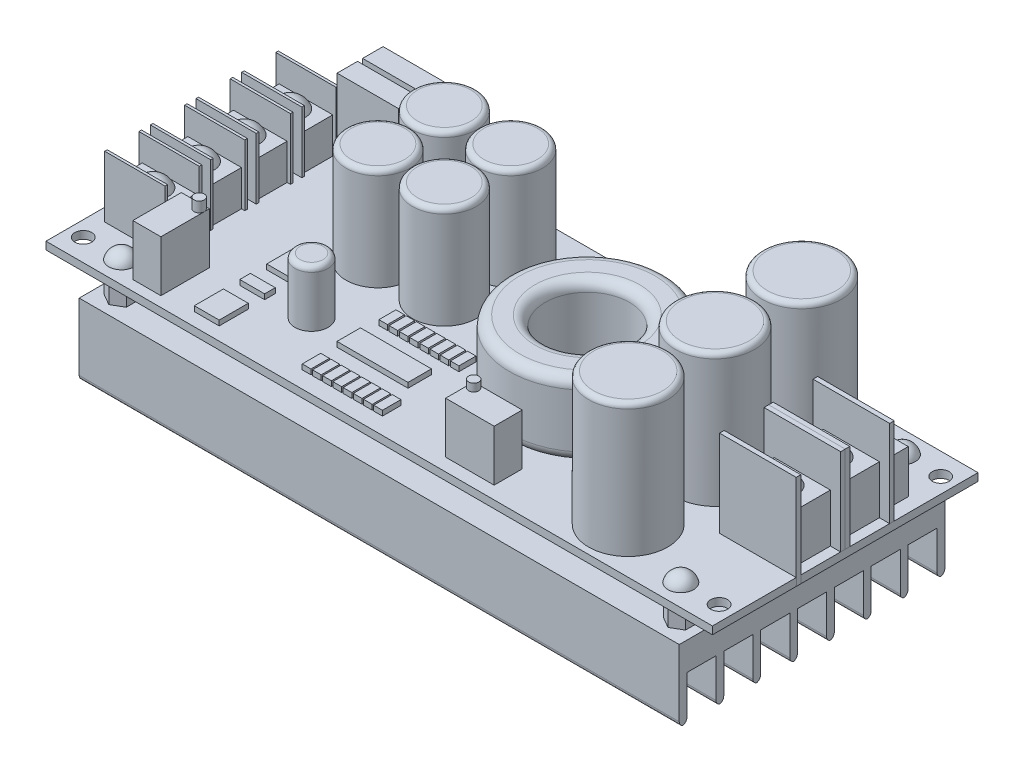
SolidWorks part; units mm, degrees
ref_plane "Alzado" through (0, 0, 0) normal (0, 0, 1) x (1, 0, 0)
ref_plane "Planta" through (0, 0, 0) normal (0, 1, 0) x (1, 0, 0)
ref_plane "Vista lateral" through (0, 0, 0) normal (1, 0, 0) x (0, 0, -1)
sketch "Croquis1" plane through (0, 0, 0) normal (0, 1, 0) x (1, 0, 0)
  line L0 (0, -26) -> (0, 26) construction
  line L1 (-65.25, 26) -> (65.25, 26)
  line L2 (-65.25, 26) -> (-65.25, -26)
  line L3 (-65.25, -26) -> (65.25, -26)
  line L4 (65.25, 26) -> (65.25, -26)
  line L5 (-65.25, 26) -> (65.25, -26) construction
  line L6 (-65.25, -26) -> (65.25, 26) construction
  line L7 (-65.25, 0) -> (65.25, 0) construction
  circle A0 centre (62.25, 21.7) radius 1.65
  circle A1 centre (62.25, -21.7) radius 1.65
  circle A2 centre (-62.25, -21.7) radius 1.65
  circle A3 centre (-62.25, 21.7) radius 1.65
  circle A4 centre (54.75, 21.7) radius 1.65
  circle A5 centre (54.75, -21.7) radius 1.65
  circle A6 centre (-54.75, -21.7) radius 1.65
  circle A7 centre (-54.75, 21.7) radius 1.65
  point P0 (0, 0)
  point P9 (0, 0)
  point P12 (0, 0)
  dimension "D3" = 3.3
  dimension "D1" = 52
  dimension "D2" = 130.5
  dimension "D4" = 3
  dimension "D5" = 4.3
  dimension "D6" = 7.5
extrude "Saliente-Extruir1" add sketch "Croquis1" along normal blind 1.5
sketch "Croquis2" plane through (0, 1.5, 0) normal (0, 1, 0) x (1, 0, 0)
  line L1 (54.75, 19.2) -> (56.9151, 20.45)
  line L2 (56.9151, 20.45) -> (56.9151, 22.95)
  line L3 (56.9151, 22.95) -> (54.75, 24.2)
  line L4 (54.75, 24.2) -> (52.5849, 22.95)
  line L5 (52.5849, 22.95) -> (52.5849, 20.45)
  line L6 (52.5849, 20.45) -> (54.75, 19.2)
  circle A0 centre (54.75, 21.7) radius 2.1651 construction
  dimension "D1" = 2.5
extrude "Saliente-Extruir2" add sketch "Croquis2" against normal blind 4.9 and the other way up to surface from surface separate body other way up to face at (-54.75, 1.5, 23.35) starting at face at (0, 0, 0)
ref_plane "Plano1" through (54.75, 0, 0) normal (1, 0, 0) x (0, 0, -1)
sketch "Croquis3" plane through (54.75, 0, 0) normal (1, 0, 0) x (0, 0, -1)
  line L0 (24.2, 1.5) -> (19.2, 1.5) construction
  line L1 (21.7, 1.5) -> (21.7, 3.5) construction
  line L2 (21.7, 1.5) -> (24.2, 1.5)
  line L3 (21.7, 1.5) -> (21.7, 3.5)
  arc A0 (21.7, 3.5) -> (24.2, 1.5) centre (21.7, 0.9375) cw
  dimension "D1" = 2
revolve "Revolución1" add sketch "Croquis3" angle 360 about L3
combine bodies "Combinar1" operation type add bodies to combine 102 103
mirror "Simetría3" about plane through (0, 0, 0) normal (0, 0, 1) of bodies 104
mirror "Simetría4" about plane through (0, 0, 0) normal (1, 0, 0) of bodies 104 108
sketch "Croquis4" plane through (0, -4.9, 0) normal (0, -1, 0) x (1, 0, 0)
  line L1 (-58.75, 26) -> (58.75, 26)
  line L2 (-58.75, 26) -> (-58.75, -26)
  line L3 (-58.75, -26) -> (58.75, -26)
  line L4 (58.75, 26) -> (58.75, -26)
  line L5 (-58.75, 26) -> (58.75, -26) construction
  line L6 (-58.75, -26) -> (58.75, 26) construction
  point P0 (0, 0)
  dimension "D1" = 52
  dimension "D2" = 117.5
extrude "Saliente-Extruir3" add sketch "Croquis4" along normal blind 5.5
sketch "Croquis5" plane through (0, -10.4, 0) normal (0, -1, 0) x (1, 0, 0)
  line L0 (58.75, -26) -> (58.75, 26) construction
  line L1 (-58.75, 26) -> (58.75, 26)
  line L2 (-58.75, 26) -> (-58.75, 24.5)
  line L3 (-58.75, 24.5) -> (58.75, 24.5)
  line L4 (58.75, 26) -> (58.75, 24.5)
  line L5 (-58.75, 18.7857) -> (-58.75, 17.2857)
  line L6 (-58.75, 18.7857) -> (58.75, 18.7857)
  line L7 (58.75, 18.7857) -> (58.75, 17.2857)
  line L8 (-58.75, 17.2857) -> (58.75, 17.2857)
  line L9 (-58.75, 11.5714) -> (-58.75, 10.0714)
  line L10 (-58.75, 11.5714) -> (58.75, 11.5714)
  line L11 (58.75, 11.5714) -> (58.75, 10.0714)
  line L12 (-58.75, 10.0714) -> (58.75, 10.0714)
  line L13 (-58.75, 4.3571) -> (-58.75, 2.8571)
  line L14 (-58.75, 4.3571) -> (58.75, 4.3571)
  line L15 (58.75, 4.3571) -> (58.75, 2.8571)
  line L16 (-58.75, 2.8571) -> (58.75, 2.8571)
  line L17 (-58.75, -2.8571) -> (-58.75, -4.3571)
  line L18 (-58.75, -2.8571) -> (58.75, -2.8571)
  line L19 (58.75, -2.8571) -> (58.75, -4.3571)
  line L20 (-58.75, -4.3571) -> (58.75, -4.3571)
  line L21 (-58.75, -10.0714) -> (-58.75, -11.5714)
  line L22 (-58.75, -10.0714) -> (58.75, -10.0714)
  line L23 (58.75, -10.0714) -> (58.75, -11.5714)
  line L24 (-58.75, -11.5714) -> (58.75, -11.5714)
  line L25 (-58.75, -17.2857) -> (-58.75, -18.7857)
  line L26 (-58.75, -17.2857) -> (58.75, -17.2857)
  line L27 (58.75, -17.2857) -> (58.75, -18.7857)
  line L28 (-58.75, -18.7857) -> (58.75, -18.7857)
  line L29 (-58.75, -24.5) -> (-58.75, -26)
  line L30 (-58.75, -24.5) -> (58.75, -24.5)
  line L31 (58.75, -24.5) -> (58.75, -26)
  line L32 (-58.75, -26) -> (58.75, -26)
  line L33 (-58.75, 26) -> (-58.75, -26) construction
  line L34 (-58.75, -26) -> (58.75, -26) construction
  dimension "D1" = 1.5
  dimension "D2" = 8
extrude "Saliente-Extruir4" add sketch "Croquis5" along normal blind 8.6
fillet "Redondeo1" radius 1 16 edges at (0, -19, -26) (0, -19, -24.5) (0, -19, -18.7857) (0, -19, -17.2857) (0, -19, -11.5714) (0, -19, -10.0714) (0, -19, -4.3571) (0, -19, -2.8571) (0, -19, 2.8571) (0, -19, 4.3571) (0, -19, 10.0714) (0, -19, 11.5714) (0, -19, 17.2857) (0, -19, 18.7857) (0, -19, 24.5) (0, -19, 26)
sketch "Croquis7" plane through (0, 0, 0) normal (0, 1, 0) x (1, 0, 0)
  line L0 (-65.25, 0) -> (65.25, 0) construction
  line L1 (-65.25, 26) -> (-65.25, -26) construction
  line L2 (65.25, -26) -> (65.25, 26) construction
  line L4 (65.25, 0) -> (50.25, 0)
  line L5 (65.25, 0) -> (65.25, -0.9)
  line L6 (65.25, -0.9) -> (50.25, -0.9)
  line L7 (50.25, 0) -> (50.25, -0.9)
  line L8 (52.25, -0.9) -> (63.25, -0.9)
  line L9 (52.25, -0.9) -> (52.25, -8.7)
  line L10 (52.25, -8.7) -> (63.25, -8.7)
  line L11 (63.25, -0.9) -> (63.25, -8.7)
  line L12 (50.25, -8.7) -> (65.25, -8.7)
  line L13 (50.25, -8.7) -> (50.25, -9.6)
  line L14 (50.25, -9.6) -> (65.25, -9.6)
  line L15 (65.25, -8.7) -> (65.25, -9.6)
  point P13 (57.75, 0)
  point P14 (57.75, -8.7)
  dimension "D1" = 0.9
  dimension "D2" = 15
  dimension "D3" = 11
  dimension "D4" = 7.8
extrude "Saliente-Extruir5" add sketch "Croquis7" along normal blind 18.5 separate body contours L15 L14 L13 L12 | L5 L6 L7 L4
sketch "Croquis8" plane through (0, 0, 0) normal (0, 1, 0) x (1, 0, 0)
  line L0 (65.25, -0.9) -> (50.25, -0.9) construction
  line L1 (52.25, -8.7) -> (63.25, -8.7) construction
  line L2 (52.25, -0.9) -> (52.25, -8.7) construction
  line L3 (63.25, -0.9) -> (63.25, -8.7) construction
  line L4 (63.25, -0.9) -> (52.25, -0.9)
  line L5 (52.25, -8.7) -> (63.25, -8.7)
  line L6 (52.25, -0.9) -> (52.25, -8.7)
  line L7 (63.25, -0.9) -> (63.25, -8.7)
extrude "Saliente-Extruir6" add sketch "Croquis8" along normal blind 11 separate body
combine bodies "Combinar2" operation type add bodies to combine 115 113 114
ref_plane "Plano2" through (57.75, 0, 0) normal (1, 0, 0) x (0, 0, -1)
sketch "Croquis9" plane through (57.75, 0, 0) normal (1, 0, 0) x (0, 0, -1)
  line L0 (-4.8, 11) -> (-4.8, 13)
  line L1 (-8.7, 11) -> (-0.9, 11) construction
  line L2 (-4.8, 11) -> (-1.8, 11)
  arc A0 (-4.8, 13) -> (-1.8, 11) centre (-4.8, 9.75) cw
  dimension "D1" = 2
  dimension "D2" = 3
revolve "Revolución2" add sketch "Croquis9" angle 360 about L0
mirror "Simetría5" about plane through (0, 0, 0) normal (0, 0, 1) of bodies 116 117
sketch "Croquis10" plane through (0, 0, 0) normal (0, 1, 0) x (1, 0, 0)
  line L0 (52.25, 8.7) -> (63.25, 8.7) construction
  line L1 (53, 15.1) -> (62.5, 15.1)
  line L2 (53, 15.1) -> (53, 10.1)
  line L3 (53, 10.1) -> (62.5, 10.1)
  line L4 (62.5, 15.1) -> (62.5, 10.1)
  line L5 (50.25, 9.6) -> (65.25, 9.6) construction
  point P6 (57.75, 8.7)
  point P7 (57.75, 10.1)
  dimension "D1" = 0.5
  dimension "D2" = 5
  dimension "D3" = 9.5
extrude "Saliente-Extruir7" add sketch "Croquis10" along normal blind 10 separate body
sketch "Croquis11" plane through (0, 10, 0) normal (0, 1, 0) x (1, 0, 0)
  line L0 (62.5, 10.1) -> (62.5, 15.1) construction
  line L1 (53, 10.1) -> (62.5, 10.1) construction
  circle A0 centre (61.5, 11.1) radius 1
  dimension "D1" = 2
extrude "Saliente-Extruir8" add sketch "Croquis11" along normal blind 1.5 separate body
sketch "Croquis12" plane through (0, 1.5, 0) normal (0, 1, 0) x (1, 0, 0)
  line L0 (65.25, -26) -> (65.25, 26) construction
  line L1 (65.25, 26) -> (-65.25, 26) construction
  line L2 (-65.25, -26) -> (65.25, -26) construction
  circle A0 centre (39.75, 17) radius 7.75
  circle A1 centre (39.75, 0) radius 7.75
  circle A2 centre (39.75, -17) radius 7.75
  dimension "D2" = 9
  dimension "15." = 15.5
  dimension "D1" = 25.5
  dimension "D4" = 9
  dimension "D3" = 3
extrude "Saliente-Extruir9" add sketch "Croquis12" along normal blind 26 separate body
sketch "Croquis14" plane through (0, 0, 0) normal (0, 0, 1) x (1, 0, 0)
  line L0 (-65.25, 1.5) -> (65.25, 1.5) construction
  line L1 (28, 1.5) -> (25, 1.5)
  line L2 (30, 3.5) -> (30, 14)
  line L3 (28, 16) -> (25, 16)
  line L4 (23, 3.5) -> (23, 14)
  line L5 (32, 27.5) -> (32, 1.5) construction
  line L6 (14.75, 1.5) -> (14.75, 16) construction
  arc A0 (28, 1.5) -> (30, 3.5) centre (28, 3.5) ccw
  arc A1 (25, 1.5) -> (23, 3.5) centre (25, 3.5) cw
  arc A2 (30, 14) -> (28, 16) centre (28, 14) ccw
  arc A3 (25, 16) -> (23, 14) centre (25, 14) ccw
  point P10 (23, 8.75)
  point P14 (30, 1.5)
  point P21 (23, 16)
  dimension "D5" = 2
  dimension "D1" = 2
  dimension "D2" = 14.5
  dimension "D3" = 7
  dimension "D4" = 8.25
revolve "Revolución3" add sketch "Croquis14" angle 360 about L6
sketch "Croquis15" plane through (0, 1.5, 0) normal (0, 1, 0) x (1, 0, 0)
  line L0 (65.25, -26) -> (65.25, 26) construction
  line L1 (10.5, -18) -> (20, -18)
  line L2 (10.5, -18) -> (10.5, -23.5)
  line L3 (10.5, -23.5) -> (20, -23.5)
  line L4 (20, -18) -> (20, -23.5)
  line L5 (-65.25, -26) -> (65.25, -26) construction
  point P4 (15.25, -18)
  dimension "D1" = 50
  dimension "D2" = 9.5
  dimension "D3" = 5.5
  dimension "D4" = 2.5
extrude "Saliente-Extruir10" add sketch "Croquis15" along normal blind 10 separate body
sketch "Croquis16" plane through (0, 11.5, 0) normal (0, 1, 0) x (1, 0, 0)
  line L0 (20, -18) -> (10.5, -18) construction
  line L1 (10.5, -18) -> (10.5, -23.5) construction
  circle A0 centre (11.5, -19) radius 1
  circle A1 centre (61.5, 11.1) radius 1 construction
extrude "Saliente-Extruir11" add sketch "Croquis16" along normal blind 1.5 separate body
fillet "Redondeo2" radius 1 1 edges at (39.75, 27.5, 24.75)
fillet "Redondeo3" radius 1 1 edges at (39.75, 27.5, 7.75)
fillet "Redondeo4" radius 1 1 edges at (39.75, 27.5, -9.25)
sketch "Croquis17" plane through (0, 1.5, 0) normal (0, 1, 0) x (1, 0, 0)
  line L0 (-65.25, 26) -> (-65.25, -26) construction
  line L1 (-62.75, 17) -> (-50.95, 17)
  line L2 (-62.75, 17) -> (-62.75, 16.5)
  line L3 (-62.75, 16.5) -> (-50.95, 16.5)
  line L4 (-50.95, 17) -> (-50.95, 16.5)
  line L5 (65.25, 26) -> (-65.25, 26) construction
  line L6 (-62.75, 10.3) -> (-62.75, 9.8)
  line L7 (-62.75, 10.3) -> (-50.95, 10.3)
  line L8 (-50.95, 10.3) -> (-50.95, 9.8)
  line L9 (-62.75, 9.8) -> (-50.95, 9.8)
  line L10 (-62.75, 1.3667) -> (-62.75, 0.8667)
  line L11 (-62.75, 0.8667) -> (-50.95, 0.8667)
  line L12 (-50.95, 1.3667) -> (-50.95, 0.8667)
  line L13 (-62.75, 1.3667) -> (-50.95, 1.3667)
  line L14 (-62.75, 8.0667) -> (-62.75, 7.5667)
  line L15 (-62.75, 8.0667) -> (-50.95, 8.0667)
  line L16 (-50.95, 8.0667) -> (-50.95, 7.5667)
  line L17 (-62.75, 7.5667) -> (-50.95, 7.5667)
  line L18 (-62.75, -7.5667) -> (-62.75, -8.0667)
  line L19 (-62.75, -8.0667) -> (-50.95, -8.0667)
  line L20 (-50.95, -7.5667) -> (-50.95, -8.0667)
  line L21 (-62.75, -7.5667) -> (-50.95, -7.5667)
  line L22 (-62.75, -0.8667) -> (-62.75, -1.3667)
  line L23 (-62.75, -0.8667) -> (-50.95, -0.8667)
  line L24 (-50.95, -0.8667) -> (-50.95, -1.3667)
  line L25 (-62.75, -1.3667) -> (-50.95, -1.3667)
  line L26 (-62.75, -16.5) -> (-62.75, -17)
  line L27 (-62.75, -17) -> (-50.95, -17)
  line L28 (-50.95, -16.5) -> (-50.95, -17)
  line L29 (-62.75, -16.5) -> (-50.95, -16.5)
  line L30 (-62.75, -9.8) -> (-62.75, -10.3)
  line L31 (-62.75, -9.8) -> (-50.95, -9.8)
  line L32 (-50.95, -9.8) -> (-50.95, -10.3)
  line L33 (-62.75, -10.3) -> (-50.95, -10.3)
  line L34 (-65.25, -26) -> (65.25, -26) construction
  dimension "D1" = 0.5
  dimension "D2" = 11.8
  dimension "D3" = 2.5
  dimension "D4" = 9
  dimension "D6" = 6.2
  dimension "D8" = 9
  dimension "D5" = 2
  dimension "D7" = 4
extrude "Saliente-Extruir12" add sketch "Croquis17" along normal blind 12 separate body
sketch "Croquis18" plane through (0, 1.5, 0) normal (0, 1, 0) x (1, 0, 0)
  line L0 (-62.75, 16.5) -> (-50.95, 16.5) construction
  line L1 (-62.1, 16.5) -> (-51.6, 16.5)
  line L2 (-62.1, 16.5) -> (-62.1, 10.3)
  line L3 (-62.1, 10.3) -> (-51.6, 10.3)
  line L4 (-51.6, 16.5) -> (-51.6, 10.3)
  line L5 (-50.95, 10.3) -> (-62.75, 10.3) construction
  line L6 (-62.75, 9.8) -> (-50.95, 9.8) construction
  line L7 (-62.1, 7.5667) -> (-62.1, 1.3667)
  line L8 (-62.1, 7.5667) -> (-51.6, 7.5667)
  line L9 (-51.6, 7.5667) -> (-51.6, 1.3667)
  line L10 (-62.1, 1.3667) -> (-51.6, 1.3667)
  line L11 (-62.1, -1.3667) -> (-62.1, -7.5667)
  line L12 (-62.1, -1.3667) -> (-51.6, -1.3667)
  line L13 (-51.6, -1.3667) -> (-51.6, -7.5667)
  line L14 (-62.1, -7.5667) -> (-51.6, -7.5667)
  line L15 (-62.1, -10.3) -> (-62.1, -16.5)
  line L16 (-62.1, -10.3) -> (-51.6, -10.3)
  line L17 (-51.6, -10.3) -> (-51.6, -16.5)
  line L18 (-62.1, -16.5) -> (-51.6, -16.5)
  point P8 (-56.85, 9.8)
  point P11 (-56.85, 16.5)
  dimension "D1" = 10.5
  dimension "D2" = 4
extrude "Saliente-Extruir13" add sketch "Croquis18" along normal blind 7 separate body
combine bodies "Combinar3" operation type add bodies to combine 136 135 134
combine bodies "Combinar4" operation type add bodies to combine 139 133 132
combine bodies "Combinar5" operation type add bodies to combine 138 131 130
combine bodies "Combinar6" operation type add bodies to combine 137 129 128
ref_plane "Plano3" through (-56.85, 0, 0) normal (1, 0, 0) x (0, 0, -1)
sketch "Croquis19" plane through (-56.85, 0, 0) normal (1, 0, 0) x (0, 0, -1)
  line L0 (13.4, 8.5) -> (13.4, 10.5)
  line L1 (16.5, 8.5) -> (10.3, 8.5) construction
  line L2 (13.4, 8.5) -> (10.4, 8.5)
  arc A0 (13.4, 10.5) -> (10.4, 8.5) centre (13.4, 7.25) ccw
  dimension "D1" = 2
  dimension "D2" = 3
revolve "Revolución4" add sketch "Croquis19" angle 360 about L0
sketch "Croquis20" plane through (-56.85, 0, 0) normal (1, 0, 0) x (0, 0, -1)
  line L0 (4.4667, 8.5) -> (4.4667, 10.5)
  line L1 (7.5667, 8.5) -> (1.3667, 8.5) construction
  line L2 (4.4667, 8.5) -> (1.4667, 8.5)
  arc A0 (4.4667, 10.5) -> (1.4667, 8.5) centre (4.4667, 7.25) ccw
  dimension "D1" = 2
  dimension "D2" = 3
revolve "Revolución5" add sketch "Croquis20" angle 360 about L0
mirror "Simetría6" about plane through (0, 0, 0) normal (0, 0, 1) of bodies 144 145
sketch "Croquis21" plane through (0, 1.5, 0) normal (0, 1, 0) x (1, 0, 0)
  line L0 (20, -18) -> (10.5, -18) construction
  line L1 (-50.25, -24) -> (-44.75, -24)
  line L2 (-50.25, -24) -> (-50.25, -14.5)
  line L3 (-50.25, -14.5) -> (-44.75, -14.5)
  line L4 (-44.75, -24) -> (-44.75, -14.5)
  line L5 (10.5, -18) -> (10.5, -23.5) construction
  line L6 (-65.25, -26) -> (65.25, -26) construction
  line L7 (-65.25, 26) -> (-65.25, -26) construction
  dimension "D1" = 2
  dimension "D2" = 15
extrude "Saliente-Extruir14" add sketch "Croquis21" along normal blind 10 separate body
sketch "Croquis22" plane through (0, 11.5, 0) normal (0, 1, 0) x (1, 0, 0)
  line L0 (-44.75, -24) -> (-44.75, -14.5) construction
  line L1 (-44.75, -14.5) -> (-50.25, -14.5) construction
  circle A0 centre (-45.75, -15.5) radius 1
  circle A1 centre (11.5, -19) radius 1 construction
extrude "Saliente-Extruir15" add sketch "Croquis22" along normal blind 2 separate body
sketch "Croquis23" plane through (0, 1.5, 0) normal (0, 1, 0) x (1, 0, 0)
  line L0 (65.25, 26) -> (-65.25, 26) construction
  line L1 (-65.25, 26) -> (-65.25, -26) construction
  circle A0 centre (-29.25, 16) radius 6.25
  circle A1 centre (-16.25, 16) radius 6.25
  circle A2 centre (-16.25, 3) radius 6.25
  circle A3 centre (-29.25, 3) radius 6.25
  dimension "D1" = 12.5
  dimension "D2" = 10
  dimension "D3" = 36
  dimension "D6" = 13
  dimension "D7" = 13
  dimension "D4" = 2
  dimension "D5" = 2
extrude "Saliente-Extruir16" add sketch "Croquis23" along normal blind 20 separate body
fillet "Redondeo5" radius 1 1 edges at (-16.25, 21.5, -9.75)
fillet "Redondeo6" radius 1 1 edges at (-16.25, 21.5, 3.25)
fillet "Redondeo7" radius 1 1 edges at (-29.25, 21.5, 3.25)
fillet "Redondeo8" radius 1 1 edges at (-29.25, 21.5, -9.75)
sketch "Croquis24" plane through (0, 1.5, 0) normal (0, 1, 0) x (1, 0, 0)
  line L0 (-65.25, -26) -> (65.25, -26) construction
  line L1 (-65.25, 26) -> (-65.25, -26) construction
  circle A0 centre (-26.25, -13) radius 3.25
  dimension "D1" = 6.5
  dimension "D2" = 13
  dimension "D3" = 39
extrude "Saliente-Extruir17" add sketch "Croquis24" along normal blind 11 separate body
fillet "Redondeo9" radius 1 1 edges at (-26.25, 12.5, 16.25)
sketch "Croquis25" plane through (0, 1.5, 0) normal (0, 1, 0) x (1, 0, 0)
  line L1 (-18.766, -10.9121) -> (-4.8653, -10.9121)
  line L2 (-18.766, -10.9121) -> (-18.766, -15.4993)
  line L3 (-18.766, -15.4993) -> (-4.8653, -15.4993)
  line L4 (-4.8653, -10.9121) -> (-4.8653, -15.4993)
  line L5 (-38.7831, -17.7235) -> (-33.9178, -17.7235)
  line L6 (-38.7831, -17.7235) -> (-38.7831, -23.4228)
  line L7 (-38.7831, -23.4228) -> (-33.9178, -23.4228)
  line L8 (-33.9178, -17.7235) -> (-33.9178, -23.4228)
  line L9 (-38.7831, -12.4412) -> (-33.9178, -12.4412)
  line L10 (-38.7831, -12.4412) -> (-38.7831, -14.5263)
  line L11 (-38.7831, -14.5263) -> (-33.9178, -14.5263)
  line L12 (-33.9178, -12.4412) -> (-33.9178, -14.5263)
  line L13 (-38.7831, -9.244) -> (-33.9178, -9.244)
  line L14 (-38.7831, -9.244) -> (-38.7831, -4.3787)
  line L15 (-38.7831, -4.3787) -> (-33.9178, -4.3787)
  line L16 (-33.9178, -9.244) -> (-33.9178, -4.3787)
extrude "Saliente-Extruir18" add sketch "Croquis25" along normal blind 1 separate body
sketch "Croquis26" plane through (0, 1.5, 0) normal (0, 1, 0) x (1, 0, 0)
  line L0 (-16.349, -7.7149) -> (-16.349, -4.3787)
  line L1 (-18.349, -19.1135) -> (-16.6396, -19.1135)
  line L2 (-18.349, -19.1135) -> (-18.349, -22.7277)
  line L3 (-18.349, -22.7277) -> (-16.6396, -22.7277)
  line L4 (-16.6396, -19.1135) -> (-16.6396, -22.7277)
  line L5 (-18.349, -7.7149) -> (-16.6809, -7.7149)
  line L6 (-18.349, -7.7149) -> (-18.349, -4.3787)
  line L7 (-18.349, -4.3787) -> (-16.6809, -4.3787)
  line L8 (-16.6809, -7.7149) -> (-16.6809, -4.3787)
  line L9 (-16.349, -7.7149) -> (-14.6809, -7.7149)
  line L10 (-14.6809, -7.7149) -> (-14.6809, -4.3787)
  line L11 (-16.349, -4.3787) -> (-14.6809, -4.3787)
  line L12 (-16.349, -19.1135) -> (-16.349, -22.7277)
  line L13 (-16.349, -19.1135) -> (-14.6396, -19.1135)
  line L14 (-14.6396, -19.1135) -> (-14.6396, -22.7277)
  line L15 (-16.349, -22.7277) -> (-14.6396, -22.7277)
  line L16 (-14.349, -7.7149) -> (-14.349, -4.3787)
  line L17 (-14.349, -7.7149) -> (-12.6809, -7.7149)
  line L18 (-12.6809, -7.7149) -> (-12.6809, -4.3787)
  line L19 (-14.349, -4.3787) -> (-12.6809, -4.3787)
  line L20 (-14.349, -19.1135) -> (-14.349, -22.7277)
  line L21 (-14.349, -19.1135) -> (-12.6396, -19.1135)
  line L22 (-12.6396, -19.1135) -> (-12.6396, -22.7277)
  line L23 (-14.349, -22.7277) -> (-12.6396, -22.7277)
  line L24 (-12.349, -7.7149) -> (-12.349, -4.3787)
  line L25 (-12.349, -7.7149) -> (-10.6809, -7.7149)
  line L26 (-10.6809, -7.7149) -> (-10.6809, -4.3787)
  line L27 (-12.349, -4.3787) -> (-10.6809, -4.3787)
  line L28 (-12.349, -19.1135) -> (-12.349, -22.7277)
  line L29 (-12.349, -19.1135) -> (-10.6396, -19.1135)
  line L30 (-10.6396, -19.1135) -> (-10.6396, -22.7277)
  line L31 (-12.349, -22.7277) -> (-10.6396, -22.7277)
  line L32 (-10.349, -7.7149) -> (-10.349, -4.3787)
  line L33 (-10.349, -7.7149) -> (-8.6809, -7.7149)
  line L34 (-8.6809, -7.7149) -> (-8.6809, -4.3787)
  line L35 (-10.349, -4.3787) -> (-8.6809, -4.3787)
  line L36 (-10.349, -19.1135) -> (-10.349, -22.7277)
  line L37 (-10.349, -19.1135) -> (-8.6396, -19.1135)
  line L38 (-8.6396, -19.1135) -> (-8.6396, -22.7277)
  line L39 (-10.349, -22.7277) -> (-8.6396, -22.7277)
  line L40 (-8.349, -7.7149) -> (-8.349, -4.3787)
  line L41 (-8.349, -7.7149) -> (-6.6809, -7.7149)
  line L42 (-6.6809, -7.7149) -> (-6.6809, -4.3787)
  line L43 (-8.349, -4.3787) -> (-6.6809, -4.3787)
  line L44 (-8.349, -19.1135) -> (-8.349, -22.7277)
  line L45 (-8.349, -19.1135) -> (-6.6396, -19.1135)
  line L46 (-6.6396, -19.1135) -> (-6.6396, -22.7277)
  line L47 (-8.349, -22.7277) -> (-6.6396, -22.7277)
  line L48 (-6.349, -7.7149) -> (-6.349, -4.3787)
  line L49 (-6.349, -7.7149) -> (-4.6809, -7.7149)
  line L50 (-4.6809, -7.7149) -> (-4.6809, -4.3787)
  line L51 (-6.349, -4.3787) -> (-4.6809, -4.3787)
  line L52 (-6.349, -19.1135) -> (-6.349, -22.7277)
  line L53 (-6.349, -19.1135) -> (-4.6396, -19.1135)
  line L54 (-4.6396, -19.1135) -> (-4.6396, -22.7277)
  line L55 (-6.349, -22.7277) -> (-4.6396, -22.7277)
  line L56 (-4.349, -7.7149) -> (-4.349, -4.3787)
  line L57 (-4.349, -7.7149) -> (-2.6809, -7.7149)
  line L58 (-2.6809, -7.7149) -> (-2.6809, -4.3787)
  line L59 (-4.349, -4.3787) -> (-2.6809, -4.3787)
  line L60 (-4.349, -19.1135) -> (-4.349, -22.7277)
  line L61 (-4.349, -19.1135) -> (-2.6396, -19.1135)
  line L62 (-2.6396, -19.1135) -> (-2.6396, -22.7277)
  line L63 (-4.349, -22.7277) -> (-2.6396, -22.7277)
  dimension "D1" = 8
extrude "Saliente-Extruir19" add sketch "Croquis26" along normal blind 1 separate body
sketch "Croquis27" plane through (0, 1.5, 0) normal (0, 1, 0) x (1, 0, 0)
  line L0 (65.25, 26) -> (-65.25, 26) construction
  line L1 (-48.25, 23) -> (-36.25, 23)
  line L2 (-48.25, 23) -> (-48.25, 19)
  line L3 (-48.25, 19) -> (-36.25, 19)
  line L4 (-36.25, 23) -> (-36.25, 19)
  line L5 (-65.25, 26) -> (-65.25, -26) construction
  line L6 (-48.25, 18) -> (-48.25, 14)
  line L7 (-48.25, 18) -> (-36.25, 18)
  line L8 (-36.25, 18) -> (-36.25, 14)
  line L9 (-48.25, 14) -> (-36.25, 14)
  dimension "D1" = 12
  dimension "D2" = 4
  dimension "D3" = 3
  dimension "D4" = 17
  dimension "D6" = 1
  dimension "D5" = 2
extrude "Saliente-Extruir20" add sketch "Croquis27" along normal blind 17 separate body
sketch "Croquis28" plane through (0, 0, -14) normal (0, 0, 1) x (1, 0, 0)
  line L1 (-44.25, 8.5) -> (-40.25, 8.5)
  line L2 (-44.25, 8.5) -> (-44.25, 1.5)
  line L3 (-44.25, 1.5) -> (-40.25, 1.5)
  line L4 (-40.25, 8.5) -> (-40.25, 1.5)
  line L5 (-48.25, 18.5) -> (-36.25, 18.5) construction
  line L6 (-65.25, 1.5) -> (65.25, 1.5) construction
  point P8 (-42.25, 18.5)
  point P9 (-42.25, 8.5)
  dimension "D1" = 4
  dimension "D2" = 7
extrude "Cortar-Extruir2" cut sketch "Croquis28" against normal blind 17 contours L4 L3 L2 L1
